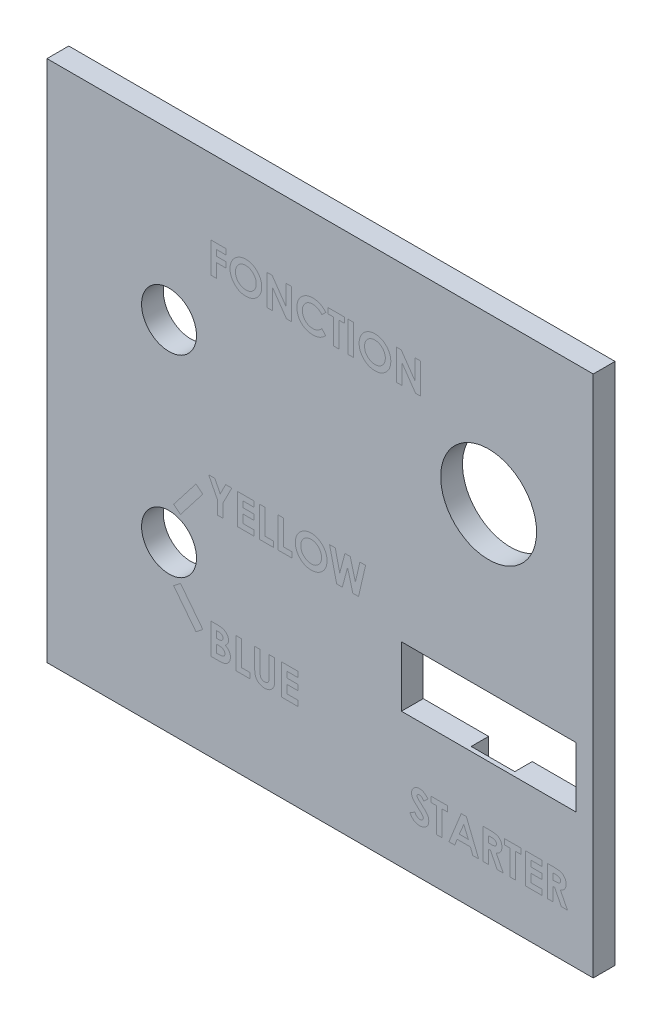
SolidWorks part; units mm, degrees
ref_plane "Plan de face" through (0, 0, 0) normal (0, 0, 1) x (1, 0, 0)
ref_plane "Plan de dessus" through (0, 0, 0) normal (0, 1, 0) x (1, 0, 0)
ref_plane "Plan de droite" through (0, 0, 0) normal (1, 0, 0) x (0, 0, -1)
sketch "Esquisse1" plane through (0, 0, 0) normal (0, 0, 1) x (1, 0, 0)
  line L1 (31.33, -30) -> (-31.33, -30)
  line L2 (31.33, -30) -> (31.33, 30)
  line L3 (31.33, 30) -> (-31.33, 30)
  line L4 (-31.33, -30) -> (-31.33, 30)
  line L5 (31.33, -30) -> (-31.33, 30) construction
  line L6 (31.33, 30) -> (-31.33, -30) construction
  point P0 (0, 0)
  dimension "D1" = 60
  dimension "D2" = 62.66
extrude "Boss.-Extru.1" add sketch "Esquisse1" along normal blind 2.5
sketch "Esquisse2" plane through (0, 0, 0) normal (0, 0, 1) x (1, 0, 0)
  line L0 (-17.33, 11.05) -> (-17.33, 30) construction
  line L1 (31.33, 30) -> (-31.33, 30) construction
  line L2 (-17.33, -11.05) -> (-17.33, -30) construction
  line L3 (-31.33, -30) -> (31.33, -30) construction
  line L4 (-31.33, 30) -> (-31.33, -30) construction
  line L5 (31.33, -30) -> (31.33, 30) construction
  line L7 (29.33, -14.5) -> (9.33, -14.5)
  line L8 (29.33, -14.5) -> (29.33, -7.6)
  line L9 (29.33, -7.6) -> (9.33, -7.6)
  line L10 (9.33, -14.5) -> (9.33, -7.6)
  line L11 (29.33, -14.5) -> (9.33, -7.6) construction
  line L12 (29.33, -7.6) -> (9.33, -14.5) construction
  circle A0 centre (-17.33, 11.05) radius 3.15
  circle A1 centre (-17.33, -11.05) radius 3.15
  circle A2 centre (19.33, 11.05) radius 5.5
  point P14 (0, 0)
  point P17 (19.33, -11.05)
  dimension "D1" = 6.3
  dimension "D2" = 6.3
  dimension "D5" = 11
  dimension "D3" = 18.95
  dimension "D4" = 14
  dimension "D6" = 12
  dimension "D7" = 6.9
  dimension "D8" = 20
  dimension "D9" = 2
extrude "Enlèv. mat.-Extru.2" cut sketch "Esquisse2" against normal through all and the other way through all
sketch "Esquisse3" plane through (0, 0, 0) normal (0, 0, -1) x (-1, 0, 0)
  line L0 (-29.33, -7.6) -> (-9.33, -7.6) construction
  line L1 (-16.83, -7.6) -> (-21.83, -7.6)
  line L2 (-16.83, -7.6) -> (-16.83, -2.6)
  line L3 (-16.83, -2.6) -> (-21.83, -2.6)
  line L4 (-21.83, -7.6) -> (-21.83, -2.6)
  line L5 (-9.33, -14.5) -> (-29.33, -14.5) construction
  line L6 (-16.83, -14.5) -> (-21.83, -14.5)
  line L7 (-16.83, -14.5) -> (-16.83, -19.5)
  line L8 (-16.83, -19.5) -> (-21.83, -19.5)
  line L9 (-21.83, -14.5) -> (-21.83, -19.5)
  point P12 (-19.33, -14.5)
  point P13 (-19.33, -7.6)
  dimension "D1" = 5
  dimension "D2" = 5
extrude "Enlèv. mat.-Extru.3" cut sketch "Esquisse3" against normal blind 2
sketch "Esquisse4" plane through (0, 0, 2.5) normal (0, 0, 1) x (1, 0, 0)
  line L0 (-12.8907, -5.5683) -> (31.33, -5.5683) construction
  line L1 (-12.8907, -19.9684) -> (31.33, -19.9684) construction
  line L2 (-12.8907, 17.8879) -> (31.33, 17.8879) construction
  line L3 (31.33, -30) -> (31.33, 30) construction
  line L4 (29.33, -24.7412) -> (9.33, -24.7412) construction
  line L5 (29.33, -14.5) -> (29.33, -7.6) construction
  line L6 (9.33, -7.6) -> (9.33, -14.5) construction
  line L7 (-17.1363, -11.05) -> (-15.2996, -11.05) construction
  line L8 (-16.7981, -7.0087) -> (-14.2402, -3.7138)
  line L9 (-16.7981, -7.0087) -> (-16.0081, -7.6219)
  line L10 (-14.2402, -3.7138) -> (-13.4503, -4.327)
  line L11 (-16.0081, -7.6219) -> (-13.4503, -4.327)
  line L12 (-16.7981, -15.0913) -> (-16.0081, -14.4781)
  line L13 (-16.0081, -14.4781) -> (-13.4503, -17.773)
  line L14 (-16.7981, -15.0913) -> (-14.2402, -18.3862)
  line L15 (-14.2402, -18.3862) -> (-13.4503, -17.773)
  circle A0 centre (-17.33, -11.05) radius 3.15 construction
  text T0 "<b>YELLOW</b>"
  text T1 "<b>BLUE</b>"
  text T2 "<b>FONCTION</b>"
  text T3 "<b>STARTER</b>"
  point P16 (-17.33, -11.05)
  dimension "D1" = 1
extrude "Enlèv. mat.-Extru.4" cut sketch "Esquisse4" against normal blind 0.1
extrude "Boss.-Extru.2" add sketch "Esquisse4<2>" against normal blind 0.1 separate body
sketch "Esquisse4<2>" plane through (0, 0, 2.5) normal (0, 0, 1) x (1, 0, 0) same geometry as "Esquisse4"
